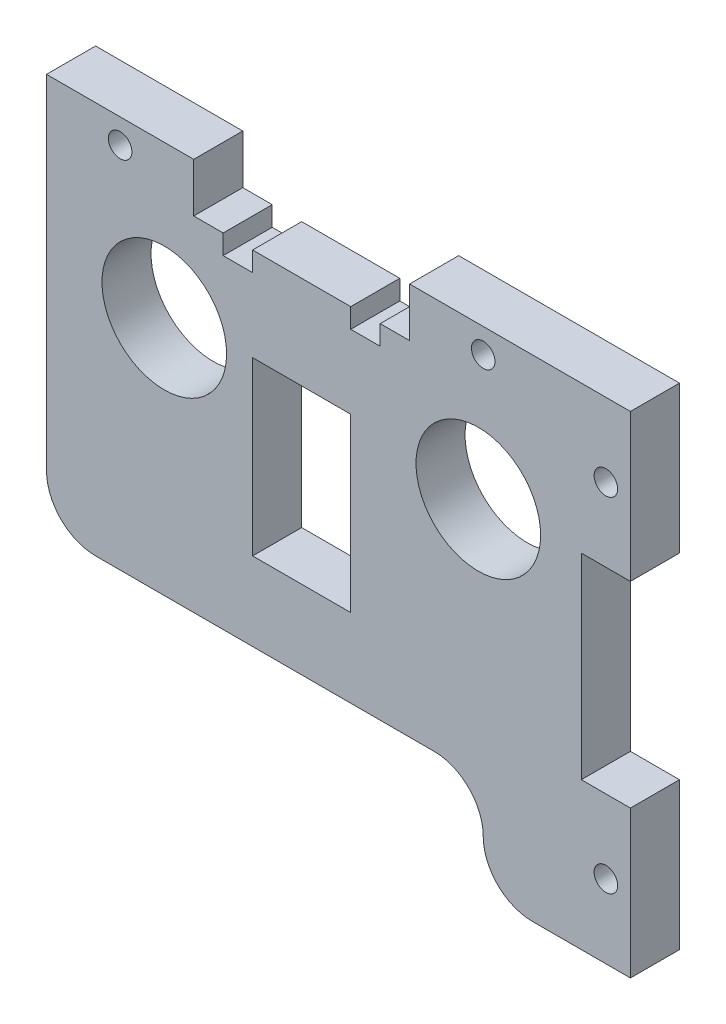
SolidWorks part; units mm, degrees
material "Acrylic (Medium-high impact)"
ref_plane "Front Plane" through (0, 0, 0) normal (0, 0, 1) x (1, 0, 0)
ref_plane "Top Plane" through (0, 0, 0) normal (0, 1, 0) x (1, 0, 0)
ref_plane "Right Plane" through (0, 0, 0) normal (1, 0, 0) x (0, 0, -1)
sketch "Sketch1" plane through (0, 0, 0) normal (0, 0, 1) x (1, 0, 0)
  line L0 (0, 40) -> (15, 40)
  line L1 (59.5, 40) -> (59.5, 25)
  line L2 (59.5, -10) -> (44.5, -10)
  line L3 (44.5, -10) -> (44.5, 0)
  line L4 (44.5, 0) -> (0, 0)
  line L5 (0, 0) -> (0, 40)
  line L6 (59.5, 25) -> (54.5, 25)
  line L7 (21, 25.5) -> (31, 25.5)
  line L8 (21, 25.5) -> (21, 8)
  line L9 (21, 8) -> (31, 8)
  line L10 (31, 25.5) -> (31, 8)
  line L11 (54.5, 25) -> (54.5, 5)
  line L12 (54.5, 5) -> (59.5, 5)
  line L13 (59.5, 5) -> (59.5, -10)
  line L14 (15, 40) -> (15, 35)
  line L15 (15, 35) -> (26, 35)
  line L16 (37, 35) -> (37, 40)
  line L17 (37, 40) -> (59.5, 40)
  line L21 (26, 35) -> (37, 35)
  circle A0 centre (12, 24.5) radius 6.35
  circle A1 centre (44, 24.5) radius 6.35
  circle A2 centre (7.5, 37.5) radius 1.2
  circle A3 centre (44.5, 37.5) radius 1.2
  circle A4 centre (57, 32.5) radius 1.2
  circle A5 centre (57, -2.5) radius 1.2
  point P15 (26, 25.5)
  point P28 (7.5, 40)
  point P33 (59.5, 32.5)
  point P34 (59.5, -2.5)
  point P41 (54.5, 5)
  dimension "D4" = 12.7
  dimension "D18" = 2.4
  dimension "D22" = 2.5
  dimension "D2" = 18
  dimension "D3" = 10
  dimension "D5" = 1
  dimension "D6" = 17.5
  dimension "D7" = 40
  dimension "D8" = 15.5
  dimension "D9" = 22
  dimension "D10" = 15.5
  dimension "D11" = 20
  dimension "D12" = 50
  dimension "D13" = 15
  dimension "D14" = 15
  dimension "D15" = 5
  dimension "D16" = 15
  dimension "D17" = 22.5
  dimension "D19" = 7.5
  dimension "D20" = 2.5
  dimension "D21" = 5
  dimension "D23" = 9
extrude "Boss-Extrude1" add sketch "Sketch1" along normal blind 5
sketch "Sketch2" plane through (0, 0, 5) normal (0, 0, 1) x (1, 0, 0)
  line L0 (18, 35) -> (18, 33)
  line L1 (37, 35) -> (15, 35) construction
  line L2 (18, 33) -> (21, 33)
  line L3 (21, 33) -> (21, 35)
  line L4 (26, 35) -> (26, 25.5) construction
  line L5 (31, 25.5) -> (21, 25.5) construction
  line L6 (18, 35) -> (21, 35)
  line L7 (15, 35) -> (15, 40) construction
  line L8 (34, 35) -> (31, 35)
  line L9 (31, 33) -> (31, 35)
  line L10 (34, 33) -> (31, 33)
  line L11 (34, 35) -> (34, 33)
  point P10 (19.5, 33)
  point P17 (32.5, 33)
  dimension "D1" = 2
  dimension "D2" = 3
  dimension "D3" = 4.5
extrude "Cut-Extrude1" cut sketch "Sketch2" against normal through all
fillet "Fillet1" radius 5 3 edges at (44.5, -10, 2.5) (44.5, 0, 2.5) (0, 0, 2.5)
